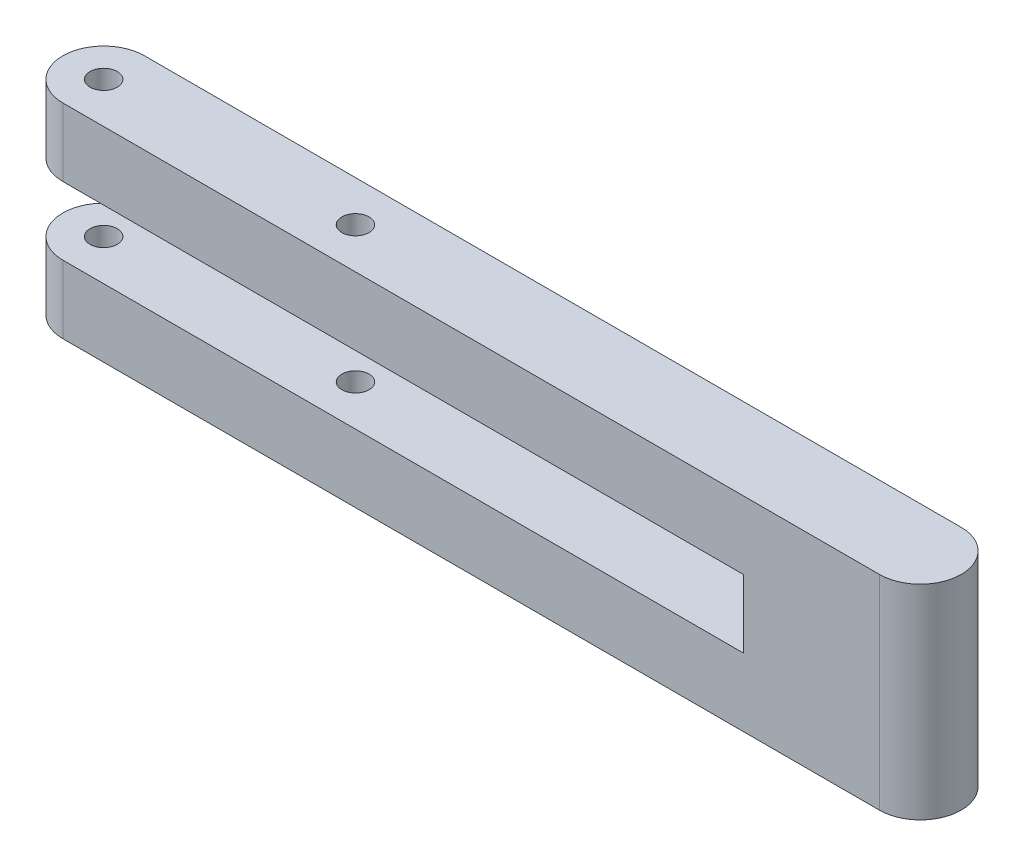
SolidWorks part; units mm, degrees
ref_plane "Front Plane" through (0, 0, 0) normal (0, 0, 1) x (1, 0, 0)
ref_plane "Top Plane" through (0, 0, 0) normal (0, 1, 0) x (1, 0, 0)
ref_plane "Right Plane" through (0, 0, 0) normal (1, 0, 0) x (0, 0, -1)
sketch "Sketch3" plane through (0, 0, 0) normal (0, 1, 0) x (1, 0, 0)
  line L0 (-63.5, 0) -> (88.9, 0) construction
  line L1 (-20.955, 0) -> (20.955, 0) construction
  line L2 (-63.5, 7.62) -> (88.9, 7.62)
  line L3 (-63.5, -7.62) -> (88.9, -7.62)
  arc A0 (-63.5, 7.62) -> (-63.5, -7.62) centre (-63.5, 0) ccw
  arc A1 (88.9, -7.62) -> (88.9, 7.62) centre (88.9, 0) ccw
  point P5 (12.7, 0)
  dimension "D2" = 7.62
  dimension "D3" = 63.5
extrude "Boss-Extrude1" add sketch "Sketch3" along normal blind 38.1
sketch "Sketch4" plane through (0, 38.1, 0) normal (0, 1, 0) x (1, 0, 0)
  circle A0 centre (-63.5, 0) radius 2.54
  circle A1 centre (-16.51, 0) radius 2.54
  dimension "D1" = 5.08
  dimension "D3" = 46.99
  dimension "D2" = 2
extrude "Cut-Extrude3" cut sketch "Sketch4" against normal through all
ref_plane "Plane2" through (0, 19.05, 0) normal (0, 1, 0) x (1, 0, 0)
sketch "Sketch5" plane through (0, 19.05, 0) normal (0, 1, 0) x (1, 0, 0)
  line L0 (0, -8.382) -> (0, 8.382) construction
  line L1 (-63.5, 7.62) -> (31.75, 7.62)
  line L2 (-63.5, -7.62) -> (0, -7.62)
  line L3 (-63.5, -7.62) -> (88.9, -7.62) construction
  line L4 (31.75, 7.62) -> (63.5, 7.62)
  line L6 (0, -7.62) -> (63.5, -7.62)
  line L7 (63.5, 7.62) -> (63.5, -7.62)
  arc A0 (-63.5, 7.62) -> (-63.5, -7.62) centre (-63.5, 0) ccw
  point P4 (-7.62, 0)
  point P9 (-16.51, 0)
  dimension "D3" = 63.5
  dimension "D1" = 7.62
  dimension "D2" = 127
  dimension "D4" = 15.24
  dimension "D5" = 63.5
  dimension "D6" = 7.62
  dimension "D7" = 7.62
  dimension "D8" = 31.75
extrude "Cut-Extrude4" cut sketch "Sketch5" against normal blind 6.35 and the other way blind 6.35 contours L6 L7 | L2 L1 | L7 L4 | L1 A0 L2 region at (-3.0032, 19.05, 0)
equation "\"TibiaLength\"= 5in"
equation "\"TibiaRadius\"= 0.3in"
equation "\"TibiaDistFromCentre\"= \"TibiaLength\" / 2"
equation "\"TibiaThickness\"= 0.5in"
equation "\"HoleRadius\"= 0.2in"
equation "\"D1@Sketch3\"= \"TibiaLength\" * 1.2"
equation "\"D2@Sketch3\"= \"TibiaRadius\""
equation "\"D3@Sketch3\"= \"TibiaDistFromCentre\""
equation "\"D1@Boss-Extrude1\"=\"TibiaThickness\"*3"
equation "\"D1@Sketch4\"= \"HoleRadius\""
equation "\"D2@Sketch5\"=\"TibiaLength\""
equation "\"D3@Sketch5\"=\"TibiaDistFromCentre\""
equation "\"D4@Sketch5\"=\"TibiaRadius\"*2"
equation "\"D5@Sketch5\"=\"TibiaDistFromCentre\""
equation "\"D7@Sketch5\"=\"TibiaRadius\""
equation "\"D8@Sketch5\"=\"TibiaDistFromCentre\"/2"
equation "\"D1@Sketch5\"=\"TibiaRadius\""
equation "\"D6@Sketch5\"=\"TibiaRadius\""
equation "\"D1@Cut-Extrude4\"= \"TibiaThickness\" * 0.5"
equation "\"D2@Cut-Extrude4\"= \"TibiaThickness\" * 0.5"
